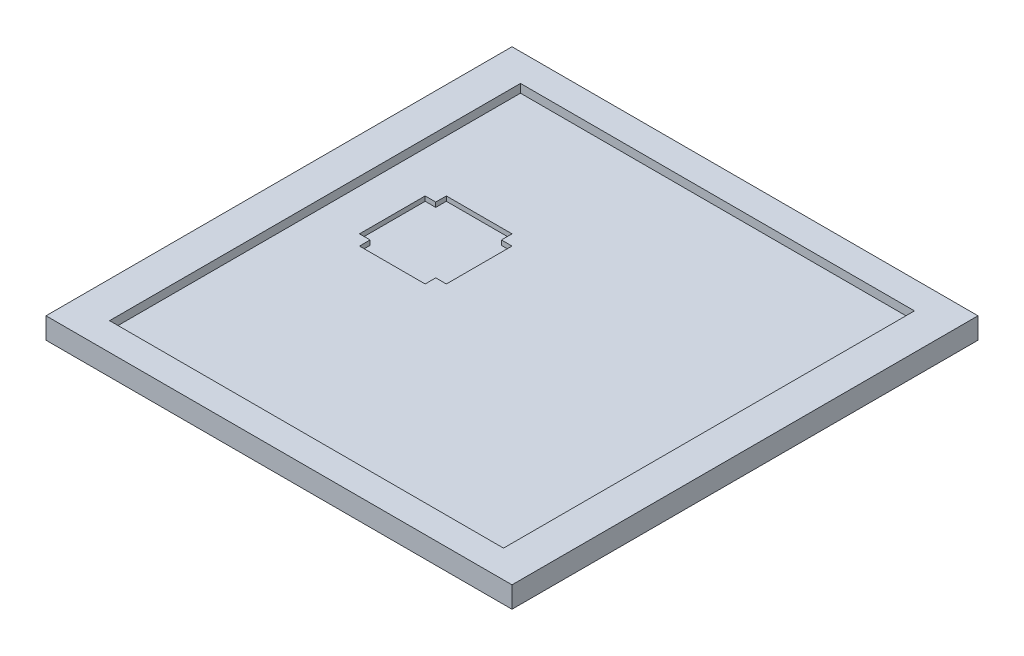
SolidWorks part; units mm, degrees
ref_plane "Front Plane" through (0, 0, 0) normal (0, 0, 1) x (1, 0, 0)
ref_plane "Top Plane" through (0, 0, 0) normal (0, 1, 0) x (1, 0, 0)
ref_plane "Right Plane" through (0, 0, 0) normal (1, 0, 0) x (0, 0, -1)
sketch "Sketch1" plane through (0, 0, 0) normal (0, 1, 0) x (1, 0, 0)
  line L1 (-68.863, 38.3493) -> (41.137, 38.3493)
  line L2 (-68.863, 38.3493) -> (-68.863, -71.6507)
  line L3 (-68.863, -71.6507) -> (41.137, -71.6507)
  line L4 (41.137, 38.3493) -> (41.137, -71.6507)
  dimension "D1" = 110
  dimension "D2" = 110
extrude "Boss-Extrude1" add sketch "Sketch1" along normal blind 5
sketch "Sketch2" plane through (0, 5, 0) normal (0, 1, 0) x (1, 0, 0)
  line L0 (41.137, 38.3493) -> (-68.863, 38.3493) construction
  line L1 (-60.363, 31.8493) -> (32.637, 31.8493)
  line L2 (-60.363, 31.8493) -> (-60.363, -65.1507)
  line L3 (-60.363, -65.1507) -> (32.637, -65.1507)
  line L4 (32.637, 31.8493) -> (32.637, -65.1507)
  line L5 (41.137, -71.6507) -> (41.137, 38.3493) construction
  point P4 (-13.863, 31.8493)
  point P7 (-13.863, 38.3493)
  point P8 (32.637, -16.6507)
  point P11 (41.137, -16.6507)
  dimension "D1" = 97
  dimension "D2" = 93
extrude "Cut-Extrude1" cut sketch "Sketch2" against normal blind 2
sketch "Sketch3" plane through (0, 3, 0) normal (0, 1, 0) x (1, 0, 0)
  line L0 (-40.363, 11.8493) -> (-40.363, -28.1507) construction
  line L1 (-60.363, 31.8493) -> (-60.363, -65.1507) construction
  line L2 (32.637, 31.8493) -> (-60.363, 31.8493) construction
  line L3 (-30.113, -0.4007) -> (-32.613, -0.4007)
  line L4 (-30.113, -0.4007) -> (-30.113, -15.9007)
  line L5 (-30.113, -15.9007) -> (-32.613, -15.9007)
  line L6 (-50.613, -0.4007) -> (-50.613, -15.9007)
  line L7 (-50.613, -0.4007) -> (-30.113, -15.9007) construction
  line L8 (-32.613, 2.0993) -> (-48.113, -18.4007) construction
  line L9 (-48.113, 2.0993) -> (-32.613, 2.0993)
  line L10 (-48.113, 2.0993) -> (-48.113, -0.4007)
  line L11 (-48.113, -18.4007) -> (-32.613, -18.4007)
  line L12 (-32.613, 2.0993) -> (-32.613, -0.4007)
  line L13 (-48.113, -0.4007) -> (-50.613, -0.4007)
  line L14 (-32.613, -15.9007) -> (-32.613, -18.4007)
  line L16 (-48.113, -15.9007) -> (-50.613, -15.9007)
  line L17 (-48.113, -15.9007) -> (-48.113, -18.4007)
  point P10 (-40.363, -8.1507)
  point P11 (-40.363, -8.1507)
  point P16 (-40.363, -8.1507)
  dimension "D1" = 20
  dimension "D2" = 20.5
  dimension "D3" = 15.5
  dimension "D4" = 20
  dimension "D5" = 40
  dimension "D6" = 15.5
  dimension "D7" = 20.5
extrude "Cut-Extrude2" cut sketch "Sketch3" against normal blind 1.1
